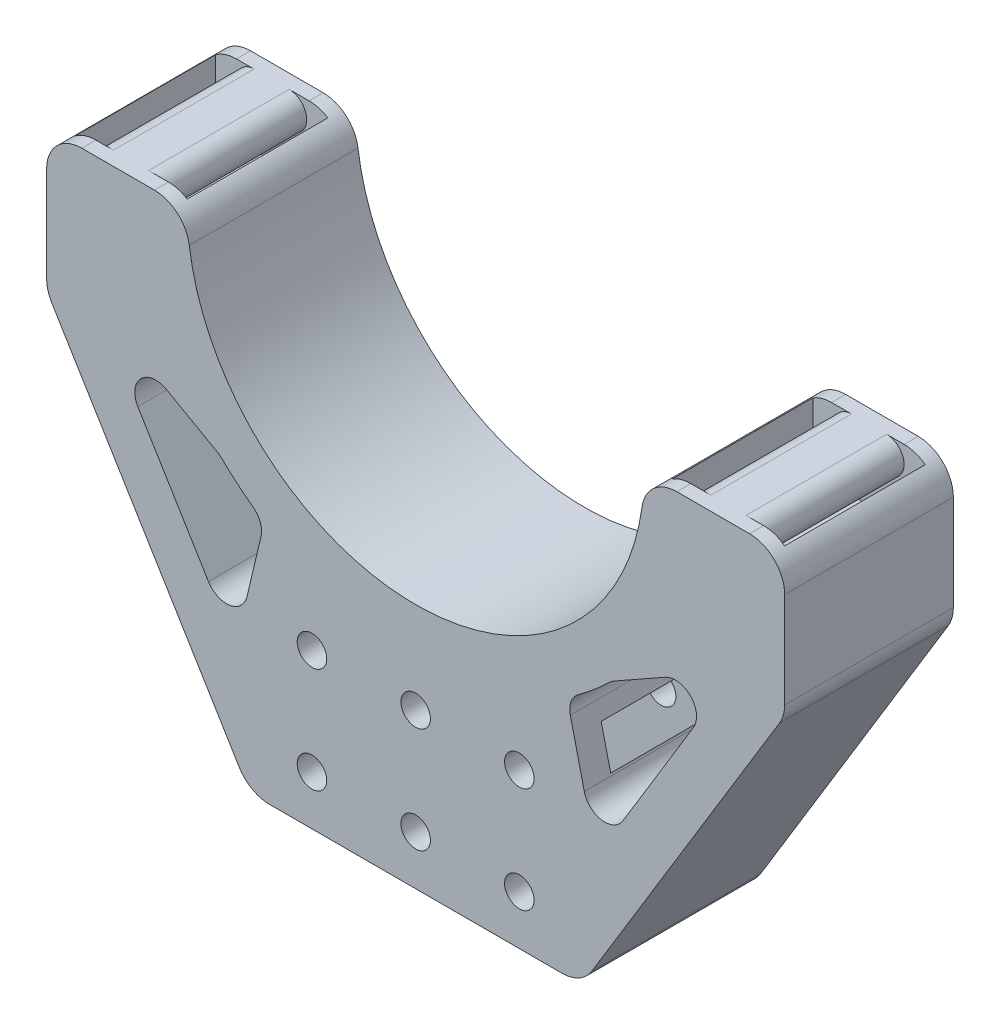
SolidWorks part; units mm, degrees
ref_plane "Front Plane" through (0, 0, 0) normal (0, 0, 1) x (1, 0, 0)
ref_plane "Top Plane" through (0, 0, 0) normal (0, 1, 0) x (1, 0, 0)
ref_plane "Right Plane" through (0, 0, 0) normal (1, 0, 0) x (0, 0, -1)
sketch "Sketch1" plane through (0, 0, 0) normal (0, 0, 1) x (1, 0, 0)
  line L0 (-41.27, 0) -> (-66.67, 0)
  line L1 (30, -85.72) -> (-30, -85.72)
  line L2 (41.27, 0) -> (66.67, 0)
  line L3 (0, 0) -> (0, -85.72) construction
  line L4 (-66.67, 0) -> (-66.67, -25.4)
  line L5 (-66.67, -25.4) -> (-30, -85.72)
  line L6 (66.67, 0) -> (66.67, -25.4)
  line L7 (66.67, -25.4) -> (30, -85.72)
  line L8 (-57.145, -3.175) -> (-50.795, -3.175) construction
  line L9 (-57.145, 0) -> (-50.795, 0)
  line L10 (-57.145, -6.35) -> (-50.795, -6.35)
  line L11 (-64.13, 0) -> (-64.13, -9.6508)
  line L12 (-57.145, -12.7) -> (-50.795, -12.7)
  line L13 (-57.145, 6.35) -> (-50.795, 6.35) construction
  line L14 (-43.81, 0) -> (-43.81, -9.6508)
  line L15 (57.145, -3.175) -> (50.795, -3.175) construction
  line L16 (57.145, 0) -> (50.795, 0)
  line L17 (57.145, -6.35) -> (50.795, -6.35)
  line L18 (43.81, 0) -> (43.81, -9.6508)
  line L19 (64.13, 0) -> (64.13, -9.6508)
  line L20 (57.145, -12.7) -> (50.795, -12.7)
  circle A0 centre (0, 0) radius 40
  circle A1 centre (0, 0) radius 41.27
  arc A2 (-57.145, 0) -> (-57.145, -6.35) centre (-57.145, -3.175) ccw
  arc A3 (-50.795, -6.35) -> (-50.795, 0) centre (-50.795, -3.175) ccw
  arc A4 (-50.795, -12.7) -> (-43.81, -9.6508) centre (-50.795, -3.175) ccw
  arc A5 (57.145, 0) -> (57.145, -6.35) centre (57.145, -3.175) cw
  arc A6 (-57.145, 6.35) -> (-57.145, -12.7) centre (-57.145, -3.175) ccw construction
  arc A7 (-50.795, -12.7) -> (-50.795, 6.35) centre (-50.795, -3.175) ccw construction
  arc A8 (-64.13, -9.6508) -> (-57.145, -12.7) centre (-57.145, -3.175) ccw
  arc A9 (50.795, -6.35) -> (50.795, 0) centre (50.795, -3.175) cw
  arc A10 (50.795, -12.7) -> (43.81, -9.6508) centre (50.795, -3.175) cw
  arc A11 (64.13, -9.6508) -> (57.145, -12.7) centre (57.145, -3.175) cw
  point P16 (-53.97, -3.175)
  point P22 (-53.97, 0)
  point P34 (53.97, -3.175)
  dimension "D1" = 44.45
  dimension "Tube" = 80
  dimension "D2" = 1.27
  dimension "D3" = 30
  dimension "D4" = 25.4
  dimension "D5" = 25.4
  dimension "D6" = 6.35
  dimension "D7" = 6.35
  dimension "D9" = 2.54
  dimension "D10" = 2.54
  dimension "D8" = 6.35
extrude "Boss-Extrude1" add sketch "Sketch1" along normal mid plane 25.4 contours L19 A11 L20 A10 L18 L2 A1 L0 L14 A4 L12 A8 L11 L4 L5 L1 L7 L6 | L10 A3 L0 A2 | A9 L17 A5 L2 region at (0, -48.726, 0) region at (-53.97, -3.175, 0) region at (53.97, -3.175, 0)
extrude "Boss-Extrude3" add sketch "Sketch1<3>" along normal blind 2.54 from vertex contours L19 A11 L20 A10 L18 L2 A1 L0 L14 A4 L12 A8 L11 L4 L5 L1 L7 L6 | L11 A8 L12 A4 L14 L0 A3 L10 A2 | L10 A3 L0 A2 | A11 L19 L2 A5 L17 A9 L18 A10 L20 | A9 L17 A5 L2 region at (0, -48.726, 0) region at (-53.97, -7.2562, 0) region at (-53.97, -3.175, 0) region at (53.97, -7.2562, 0) region at (53.97, -3.175, 0) starting at point (-43.81, 0, 12.7)
sketch "Sketch1<3>" plane through (0, 0, 0) normal (0, 0, 1) x (1, 0, 0) same geometry as "Sketch1"
extrude "Boss-Extrude4" add sketch "Sketch1<4>" against normal blind 2.54 from vertex contours L10 A3 L0 A2 | L11 A8 L12 A4 L14 L0 A3 L10 A2 | L19 A11 L20 A10 L18 L2 A1 L0 L14 A4 L12 A8 L11 L4 L5 L1 L7 L6 | A9 L17 A5 L2 | A11 L19 L2 A5 L17 A9 L18 A10 L20 region at (0, -48.726, 0) region at (-53.97, -7.2562, 0) region at (-53.97, -3.175, 0) region at (53.97, -7.2562, 0) region at (53.97, -3.175, 0) starting at point (-43.81, 0, -12.7)
sketch "Sketch1<4>" plane through (0, 0, 0) normal (0, 0, 1) x (1, 0, 0) same geometry as "Sketch1"
fillet "Fillet2" radius 6.35 8 edges at (-66.67, 0, 0) (-41.27, 0, 0) (41.27, 0, 0) (66.67, 0, 0) (66.67, -25.4, 0) (30, -85.72, 0) (-30, -85.72, 0) (-66.67, -25.4, 0)
sketch "Sketch2" plane through (0, -85.72, 0) normal (0, -1, 0) x (1, 0, 0)
  line L1 (30.381, 10.381) -> (-30.381, 10.381)
  line L2 (30.381, 10.381) -> (30.381, -10.381)
  line L3 (30.381, -10.381) -> (-30.381, -10.381)
  line L4 (-30.381, 10.381) -> (-30.381, -10.381)
  line L5 (30.381, 10.381) -> (-30.381, -10.381) construction
  line L6 (30.381, -10.381) -> (-30.381, 10.381) construction
  point P0 (0, 0)
  dimension "D1" = 60.762
  dimension "D2" = 20.762
extrude "Cut-Extrude1" cut sketch "Sketch2" against normal blind 38.1
sketch "Sketch3" plane through (0, 0, 15.24) normal (0, 0, 1) x (1, 0, 0)
  line L0 (0, -41.27) -> (0, -85.72) construction
  line L1 (26.429, -85.72) -> (-26.429, -85.72) construction
  line L2 (-18.7325, -57.78) -> (18.7325, -57.78) construction
  line L3 (-18.7325, -76.83) -> (18.7325, -76.83) construction
  arc A0 (-40.9014, -5.5032) -> (40.9014, -5.5032) centre (0, 0) ccw construction
  circle A1 centre (0, -57.78) radius 2.667
  circle A2 centre (0, -76.83) radius 2.667
  circle A3 centre (-18.7325, -57.78) radius 2.159 construction
  circle A4 centre (18.7325, -57.78) radius 2.159 construction
  circle A5 centre (-18.7325, -57.78) radius 2.667
  circle A6 centre (18.7325, -57.78) radius 2.667
  circle A7 centre (-18.7325, -76.83) radius 2.667
  circle A8 centre (18.7325, -76.83) radius 2.667
  circle A9 centre (18.7325, -76.83) radius 2.159 construction
  circle A10 centre (-18.7325, -76.83) radius 2.159 construction
  point P15 (0, -57.78)
  dimension "D2" = 5.334
  dimension "D4" = 4.318
  dimension "D5" = 35.306
  dimension "D1" = 19.05
  dimension "D3" = 8.89
  dimension "D7" = 19.05
  dimension "D6" = 2
extrude "Cut-Extrude2" cut sketch "Sketch3" against normal through all
sketch "Sketch4" plane through (0, 0, 15.24) normal (0, 0, 1) x (1, 0, 0)
  line L0 (0, -41.27) -> (0, -85.72) construction
  line L1 (26.429, -85.72) -> (-26.429, -85.72) construction
  line L2 (57.78, -22.9098) -> (32.6206, -64.2955)
  line L3 (32.6206, -64.2955) -> (27.3408, -42.0536)
  line L4 (57.78, -22.9098) -> (35.3767, -35.56)
  line L7 (-57.78, -22.9098) -> (-35.3767, -35.56)
  line L8 (-32.6206, -64.2955) -> (-27.3408, -42.0536)
  line L14 (-49.3659, -8.89) -> (-57.78, -8.89)
  line L15 (-57.78, -8.89) -> (-57.78, -22.9098)
  line L16 (-57.78, -22.9098) -> (-25.0006, -76.83)
  line L17 (-25.0006, -76.83) -> (25.0006, -76.83)
  line L18 (25.0006, -76.83) -> (57.78, -22.9098)
  line L19 (57.78, -22.9098) -> (57.78, -8.89)
  line L20 (57.78, -8.89) -> (49.3659, -8.89)
  line L23 (-57.78, -22.9098) -> (-32.6206, -64.2955)
  arc A0 (-40.9014, -5.5032) -> (40.9014, -5.5032) centre (0, 0) ccw construction
  arc A1 (35.3767, -35.56) -> (27.3408, -42.0536) centre (0, 0) cw
  arc A18 (-49.3659, -8.89) -> (49.3659, -8.89) centre (0, 0) ccw
  arc A19 (-35.3767, -35.56) -> (-27.3408, -42.0536) centre (0, 0) ccw
  dimension "D2" = 22.86
  dimension "D3" = 7.62
  dimension "D4" = 35.56
  dimension "D1" = 8.89
extrude "Cut-Extrude3" cut sketch "Sketch4" against normal through all
fillet "Fillet3" radius 3.81 8 edges at (57.78, -22.9098, 0) (32.6206, -64.2955, 0) (27.3408, -42.0536, 0) (35.3767, -35.56, 0) (-35.3767, -35.56, 0) (-27.3408, -42.0536, 0) (-32.6206, -64.2955, 0) (-57.78, -22.9098, 0)
